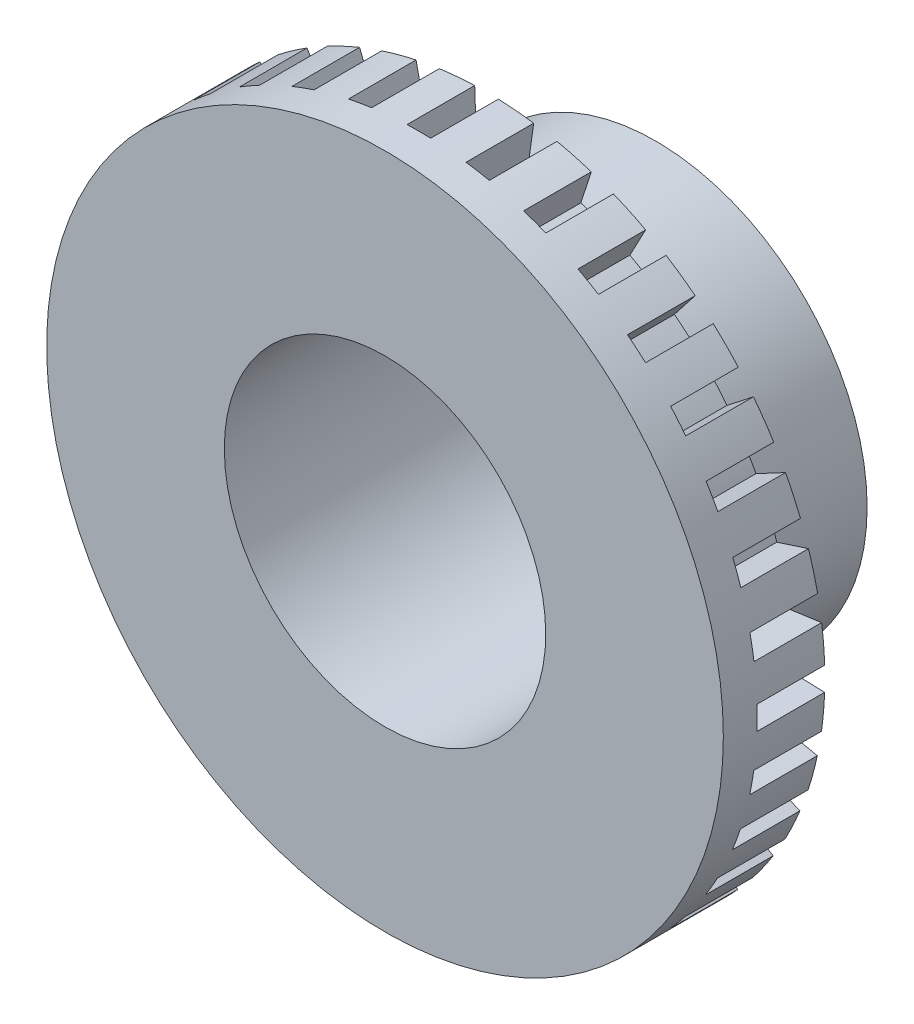
SolidWorks part; units mm, degrees
note: '?' marks a value the reader was unsure of. The reader was unsure of these and kept them because the rebuilt part matched: shared geometry of "Sketch1<3>", "Sketch1<4>", "Sketch1<5>", "Sketch1<6>".
ref_plane "Front Plane" through (0, 0, 0) normal (0, 0, 1) x (1, 0, 0)
ref_plane "Top Plane" through (0, 0, 0) normal (0, 1, 0) x (1, 0, 0)
ref_plane "Right Plane" through (0, 0, 0) normal (1, 0, 0) x (0, 0, -1)
sketch "Sketch1" plane through (0, 0, 0) normal (0, 0, 1) x (1, 0, 0)
  line L0 (0, 0) -> (0, 27.5) construction
  line L1 (0, 0) -> (-0.3315, 9.4942) construction
  line L2 (0, 0) -> (0.3315, 9.4942) construction
  line L3 (0.6282, 17.989) -> (0.698, 19.9878)
  line L4 (-0.6282, 17.989) -> (-0.698, 19.9878)
  line L5 (0, 0) -> (9.5, 0) construction
  line L6 (7.4715, 0.6537) -> (9.4638, 0.828)
  line L7 (7.4715, -0.6537) -> (9.4638, -0.828)
  line L8 (7.4715, -0.6537) -> (0, 0) construction
  line L9 (0, 0) -> (7.4715, 0.6537) construction
  circle A0 centre (0, 0) radius 12.5
  circle A1 centre (0, 0) radius 20
  circle A2 centre (0, 0) radius 57.5 construction
  circle A3 centre (0, 0) radius 40 construction
  circle A4 centre (0, 0) radius 9.5
  circle A5 centre (0, 0) radius 27.5 construction
  circle A6 centre (0, 0) radius 18
  arc A7 (7.4715, 0.6537) -> (7.4715, -0.6537) centre (0, 0) cw
  dimension "D1" = 25
  dimension "D2" = 40
  dimension "D3" = 115
  dimension "D4" = 80
  dimension "D5" = 19
  dimension "D6" = 55
  dimension "D8" = 36
  dimension "D7" = 2
  dimension "D10" = 2
  dimension "D9" = 5
extrude "Boss-Extrude1" add sketch "Sketch1" along normal blind 4 contours A1 A0 | L2 A6 L1 A0 | A4 L2 A0 L1 | A6 L1 A1 L2 | A6 L2 A1 L1 | A4 L1 A0 L2 | L1 A4 L2
extrude "Cut-Extrude1" cut sketch "Sketch1<3>" along normal blind 4.5 contours A6 L2 A1 L1
sketch "Sketch1<3>" plane through (0, 0, 0) normal (0, 0, 1) x (1, 0, 0) same geometry as "Sketch1"
pattern_circular "CirPattern2" count 36 over 360 about axis through (0, -0.0402, 0) along (0, 0, 1) of "Cut-Extrude1"
extrude "Cut-Extrude2" cut sketch "Sketch1<4>" along normal blind 10 contours A4
sketch "Sketch1<4>" plane through (0, 0, 0) normal (0, 0, 1) x (1, 0, 0) same geometry as "Sketch1"
extrude "Boss-Extrude2" add sketch "Sketch1<5>" against normal blind 10 contours A4 L1 A0 L2 | A4 L2 A0 L1
sketch "Sketch1<5>" plane through (0, 0, 0) normal (0, 0, 1) x (1, 0, 0) same geometry as "Sketch1"
extrude "Boss-Extrude3" add sketch "Sketch1<6>" along normal blind 4 and the other way blind 10 contours L6 A7 L7 A4
sketch "Sketch1<6>" plane through (0, 0, 0) normal (0, 0, 1) x (1, 0, 0) same geometry as "Sketch1"
ref_axis "Axis1" through (0, 0, 0) along (0, 0, 1)?
sketch "Sketch3" plane through (0, 0, 4) normal (0, 0, 1) x (1, 0, 0)
  circle A1 centre (0, 0) radius 20
  circle A2 centre (0, 0) radius 9.5
  dimension "D2" = 40
  dimension "D1" = 19
extrude "Boss-Extrude6" add sketch "Sketch3" along normal blind 2
equation "\"tyre_ID\"= 115mm"
equation "\"disc_OD\" = 80mm"
equation "\"discbell_OD\" = 55mm"
equation "\"hub_OD\" = 40"
equation "\"bearing_ID\" = 25mm"
equation "\"shaft_OD\"= 19mm"
equation "\"D3@Sketch1\"=\"tyre_ID\""
equation "\"D6@Sketch1\"=\"discbell_OD\""
equation "\"D4@Sketch1\"=\"disc_OD\""
equation "\"D2@Sketch1\"=\"hub_OD\""
equation "\"D8@Sketch1\"=\"hub_OD\"-4"
equation "\"D1@Sketch1\"=\"bearing_ID\""
equation "\"D5@Sketch1\"=\"shaft_OD\""
equation "\"D2@Sketch3\"=\"hub_OD\""
equation "\"D1@Sketch3\"=\"shaft_OD\""
